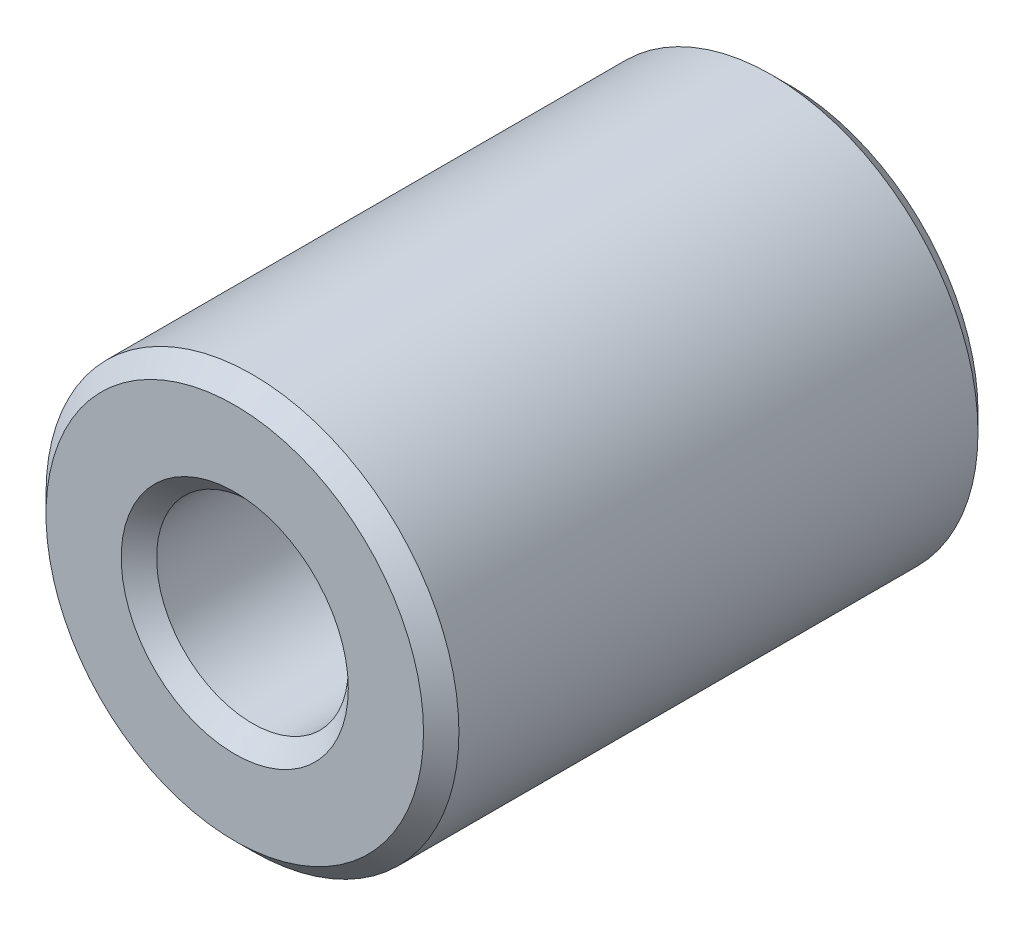
SolidWorks part; units mm, degrees
ref_plane "Front Plane" through (0, 0, 0) normal (0, 0, 1) x (1, 0, 0)
ref_plane "Top Plane" through (0, 0, 0) normal (0, 1, 0) x (1, 0, 0)
ref_plane "Right Plane" through (0, 0, 0) normal (1, 0, 0) x (0, 0, -1)
sketch "Sketch2" plane through (0, 0, 0) normal (0, 0, 1) x (1, 0, 0)
  circle A0 centre (0, 0) radius 3.5
  circle A1 centre (0, 0) radius 1.625
  dimension "D1" = 3.25
  dimension "D2" = 7
extrude "Boss-Extrude1" add sketch "Sketch2" along normal blind 9.4
chamfer "Chamfer1" distance 0.3 angle 45 4 edges at (3.5, 0, 0) (3.5, 0, 9.4) (1.625, 0, 0) (1.625, 0, 9.4)
